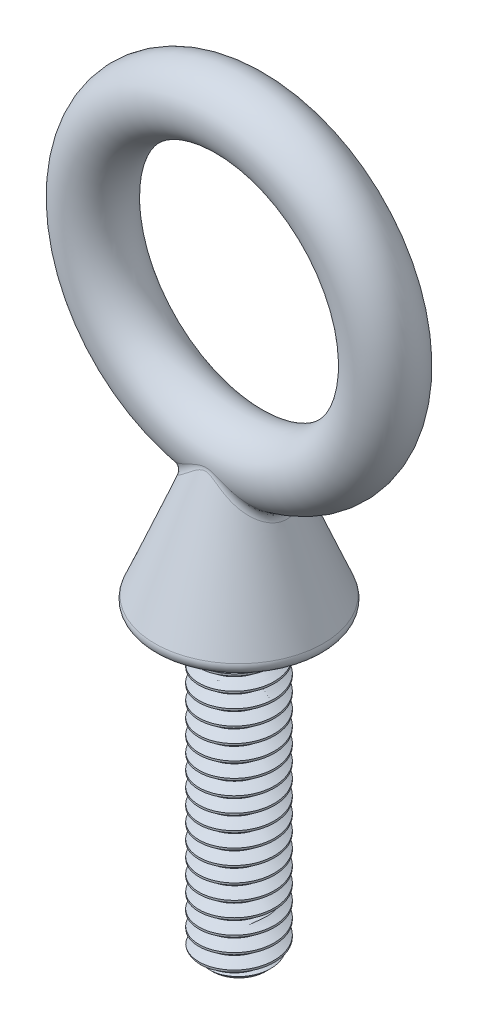
SolidWorks part; units mm, degrees
note: '?' marks a value the reader was unsure of.
ref_plane "Front Plane" through (0, 0, 0) normal (0, 0, 1) x (1, 0, 0)
ref_plane "Top Plane" through (0, 0, 0) normal (0, 1, 0) x (1, 0, 0)
ref_plane "Right Plane" through (0, 0, 0) normal (1, 0, 0) x (0, 0, -1)
sketch "Sketch1" plane through (0, 0, 0) normal (0, 0, 1) x (1, 0, 0)
  line L0 (0, -15.0812) -> (0, -49.2125) construction
  line L1 (-3.175, -49.2125) -> (3.175, -49.2125) construction
  line L2 (3.3125, -49.1331) -> (3.3125, -50.4031) construction
  line L3 (0, -15.0812) -> (0, -9.525) construction
  line L4 (-7.1437, -23.8125) -> (7.1438, -23.8125) construction
  line L5 (3.3125, -50.4031) -> (2.2126, -49.7681) construction
  line L6 (2.2126, -49.7681) -> (3.3125, -49.1331) construction
  line L7 (2.2126, -49.7681) -> (2.3501, -49.7681) construction
  line L8 (3.3125, -49.7681) -> (3.175, -49.7681) construction
  line L9 (2.3501, -49.8475) -> (2.3501, -49.6887) construction
  line L10 (3.175, -50.3238) -> (3.175, -49.2125) construction
  line L11 (3.2437, -50.3634) -> (3.2437, -49.1728) construction
  circle A0 centre (0, 0) radius 15.0813 construction
  circle A1 centre (0, 12.3031) radius 2.7781 construction
  circle A2 centre (0, 0) radius 9.525 construction
  point P7 (0, -15.0812)
  point P9 (0, -23.8125)
  point P10 (0, 15.0812)
  point P11 (0, 9.525)
  point P14 (0, -49.2125)
  point P17 (0, 0)
  point P19 (0, -12.3031)
  point P21 (0, -23.8125)
  point P32 (2.3501, -49.7681)
  point P35 (3.175, -49.7681)
  point P38 (3.2437, -49.7681)
  dimension "Pitch" = 1.27
  dimension "D1" = 0.1588
sketch "Sketch2" plane through (0, 0, 0) normal (0, 1, 0) x (1, 0, 0)
  circle A0 centre (0, 0) radius 3.175
extrude "Boss-Extrude1" add sketch "Sketch2" against normal up to vertex (49.2125 mm away) from vertex at -23.8125 starting at point (0, -23.8125, 0)
sketch "Sketch3" plane through (0, -49.2125, 0) normal (0, -1, 0) x (1, 0, 0)
  circle A1 centre (0, 0) radius 3.175
  circle A2 centre (0, 0) radius 3.175
  point P0 (3.175, 0)
  point P1 (0, -3.175)
  dimension "D1" = 0
sketch "Sketch4" plane through (0, 0, 0) normal (0, 0, 1) x (1, 0, 0)
  line L0 (2.3501, -49.6887) -> (2.3501, -49.8475)
  line L1 (2.3501, -49.8475) -> (3.2437, -50.3634)
  line L2 (3.2437, -50.3634) -> (3.2437, -49.1728)
  line L3 (3.2437, -49.1728) -> (2.3501, -49.6887)
sketch "Sketch5" plane through (0, -49.2125, 0) normal (0, -1, 0) x (1, 0, 0)
  circle A0 centre (0, 0) radius 2.2126
extrude "Cut-Extrude1" cut sketch "Sketch5" against normal through all draft 45 flip side to cut
sketch "Sketch6" plane through (0, 0, 0) normal (1, 0, 0) x (0, 0, -1)
  circle A0 centre (0, 12.3031) radius 2.7781
ref_axis "Axis1" through (0, 0, -7.6398) along (0, 0, 1)
revolve "Revolve1" add sketch "Sketch6" angle 360 about axis through (0, 0, -7.6398) along (0, 0, 1)
sketch "Sketch8" plane through (0, 0, 0) normal (0, 0, 1) x (1, 0, 0)
  line L0 (0, -23.8125) -> (0, -12.3031)
  line L1 (0, -12.3031) -> (-2.7781, -12.3031)
  line L2 (-6.4492, -23.8125) -> (-7.1437, -23.8125) construction
  line L3 (-7.1437, -23.8125) -> (-7.1437, -23.118) construction
  line L4 (0, -23.8125) -> (7.1437, -23.8125) construction
  line L5 (-7.1437, -23.8125) -> (7.1438, -23.8125) construction
  line L6 (-7.0921, -22.8551) -> (-2.7781, -12.3031)
  line L7 (-7.1437, -23.8125) -> (0, -23.8125) construction
  line L9 (-6.4492, -23.8125) -> (0, -23.8125)
  arc A0 (-7.0921, -22.8551) -> (-6.4492, -23.8125) centre (-6.4492, -23.118) ccw
  circle A1 centre (0, -12.3031) radius 2.7781 construction
  dimension "D1" = 0.6945
revolve "Revolve2" add sketch "Sketch8" angle 360 about L0
fillet "Fillet1" radius 0.6945 1 edges at (3.2544, -14.2744, 1.5013)
sketch "SketchX" plane through (0, 0, 0) normal (1, 0, 0) x (0, 0, -1)
  line L0 (3.175, -49.2125) -> (3.175, -46.0375) construction
  line L1 (0, -49.2125) -> (3.175, -49.2125) construction
  dimension "D1" = 3.175
  dimension "D2" = 3.175
ref_axis "Center Axis 1" through (0, 21.5506, 0) along (0, -1, 0)?
ref_axis "Center Axis 2" through (0, 0, -7.6398) along (0, 0, 1)?
curve "Helix/Spiral1" pitch 1.27 height 26.67 turns 21 parameters "Pitch"=1.27
ref_plane "Plane1" through (0, -23.8125, 0) normal (0, -1, 0) x (1, 0, 0)
split "Split1" trim tools "Plane1" bodies to split 109 resulting bodies 110 111
sweep "Cut-Sweep1" cut profiles "Sketch4" path "Helix/Spiral1" align with end faces yes
sketch "Sketch9" plane through (0, -23.8125, 0) normal (0, -1, 0) x (1, 0, 0)
  line L0 (-7.1437, 0) -> (7.1438, 0) construction
  circle A0 centre (0, 0) radius 3.175
extrude "Boss-Extrude2" add sketch "Sketch9" along normal blind 2.54 draft 45
equation "\"D3@Helix/Spiral1\" = \"Pitch@Helix/Spiral1\" + \"Thread Lg.@Sketch1\""
equation "\"D1@Sketch8\" = \"A@Sketch1\" / 8"
equation "\"D1@Fillet1\" = \"A@Sketch1\" / 8"
equation "\"D1@SketchX\"= \"Pitch@Helix/Spiral1\"*2.5"
equation "\"D1@Sketch1\"=\"Pitch@Sketch1\"/8"
equation "\"Pitch@Helix/Spiral1\"=\"Pitch@Sketch1\""
equation "\"D2@SketchX\" = \"Thread OD@Sketch1\" / 2"
